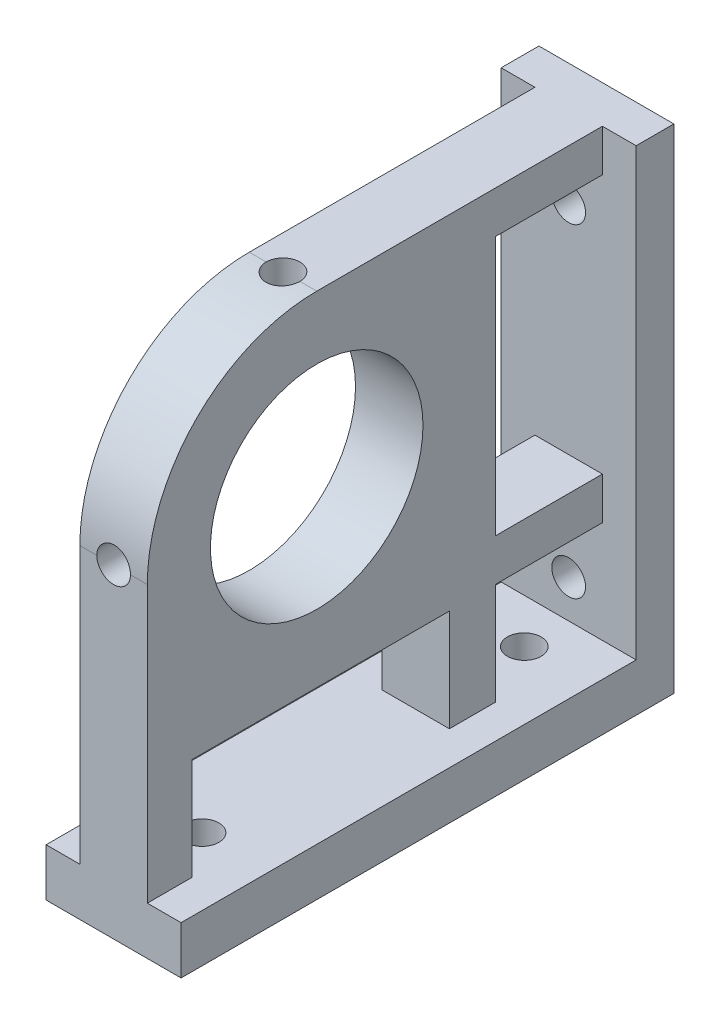
SolidWorks part; units mm, degrees
ref_plane "Front Plane" through (0, 0, 0) normal (0, 0, 1) x (1, 0, 0)
ref_plane "Top Plane" through (0, 0, 0) normal (0, 1, 0) x (1, 0, 0)
ref_plane "Right Plane" through (0, 0, 0) normal (1, 0, 0) x (0, 0, -1)
sketch "Sketch1" plane through (0, 0, 0) normal (1, 0, 0) x (0, 0, -1)
  line L11 (0, 31.8822) -> (31.8822, 31.8822)
  line L12 (31.8822, 31.8822) -> (60.8746, 31.8822)
  line L16 (60.8746, 31.8822) -> (60.8746, -60.96)
  line L17 (-31.8822, 0) -> (-31.8822, -60.96)
  line L18 (60.8746, -60.96) -> (-31.8822, -60.96)
  circle A1 centre (0, 0) radius 20
  arc A3 (0, 31.8822) -> (-31.8822, 0) centre (0, 0) ccw
extrude "Boss-Extrude1" add sketch "Sketch1" along normal blind 12.7
sketch "Sketch8" plane through (12.7, 0, 0) normal (1, 0, 0) x (0, 0, -1)
  line L0 (-31.8822, -60.96) -> (60.8746, -60.96) construction
  line L1 (60.8746, 31.8822) -> (53.7706, 31.8822)
  line L2 (60.8746, 31.8822) -> (60.8746, -60.96)
  line L3 (60.8746, -60.96) -> (53.7706, -60.96)
  line L4 (53.7706, 31.8822) -> (53.7706, -51.9379)
  line L5 (-31.8822, 0) -> (-31.8822, -60.96) construction
  line L6 (53.7706, -60.96) -> (-31.8822, -60.96)
  line L8 (53.7706, -51.9379) -> (-31.8822, -51.9379)
  line L9 (-31.8822, -60.96) -> (-31.8822, -51.9379)
extrude "Boss-Extrude2" add sketch "Sketch8" along normal blind 6.35 and the other way blind 19.05
sketch "Sketch2" plane through (0, 0, 0) normal (0, 1, 0) x (1, 0, 0)
  circle A0 centre (6.35, 0) radius 3.175
extrude "Cut-Extrude1" cut sketch "Sketch2" along normal through all
sketch "Sketch10" plane through (0, 0, 31.8822) normal (0, 0, 1) x (1, 0, 0)
  line L0 (12.7, 0) -> (0, 0) construction
  circle A0 centre (6.35, 0) radius 3.175
extrude "Cut-Extrude6" cut sketch "Sketch10" against normal blind 8.128
fillet "Fillet1" [suppressed] radius 2.54
mirror "Mirror1" [suppressed] about plane through (0, 0, 0) normal (0, 0, 1)
fillet "Fillet2" [suppressed] radius 5.08
sketch "Sketch4" plane through (0, 0, 0) normal (-1, 0, 0) x (0, 0, 1)
  line L4 (-53.7706, 23.9633) -> (-33.6922, 23.9633)
  line L5 (-33.6922, 23.9633) -> (-33.6922, -24.8177)
  line L6 (-24.9665, -32.7419) -> (23.4543, -32.7419)
  line L7 (23.4543, -32.7419) -> (23.4543, -51.9379)
  line L8 (23.4543, -51.9379) -> (-24.9665, -51.9379)
  line L9 (-53.7706, -51.9379) -> (-53.7706, -32.7419)
  line L10 (-33.6922, -32.7419) -> (-33.6922, -51.9379)
  line L11 (-24.9665, -51.9379) -> (-24.9665, -32.7419)
  line L12 (-33.6922, -51.9379) -> (-53.7706, -51.9379)
  line L13 (-33.6922, -32.7419) -> (-53.7706, -32.7419)
  line L14 (-33.6922, -24.8177) -> (-53.7706, -24.8177)
  line L15 (-53.7706, -24.8177) -> (-53.7706, 23.9633)
extrude "Cut-Extrude2" cut sketch "Sketch4" against normal blind 26.162
sketch "Sketch5" plane through (0, 0, -60.8746) normal (0, 0, -1) x (-1, 0, 0)
  circle A0 centre (-6.35, 16.187) radius 3.175
  circle A1 centre (-6.35, -44.7886) radius 3.175
extrude "Cut-Extrude3" cut sketch "Sketch5" against normal blind 11.43
sketch "Sketch6" plane through (0, -60.96, 0) normal (0, -1, 0) x (1, 0, 0)
  circle A0 centre (6.35, 15.24) radius 3.175
  circle A1 centre (6.35, -45.4106) radius 3.175
extrude "Cut-Extrude4" cut sketch "Sketch6" against normal blind 11.43
sketch "Sketch9" plane through (0, 0, 0) normal (-1, 0, 0) x (0, 0, 1)
  line L1 (-33.6922, -24.8177) -> (-71.3105, -24.8177)
  line L2 (-33.6922, -24.8177) -> (-33.6922, 42.9585)
  line L3 (-33.6922, 42.9585) -> (-71.3105, 42.9585)
  line L4 (-71.3105, -24.8177) -> (-71.3105, 42.9585)
extrude "Cut-Extrude5" [suppressed] cut sketch "Sketch9" against normal blind 41.656 and the other way blind 46.736
fillet "Fillet3" [suppressed] radius 33.02
